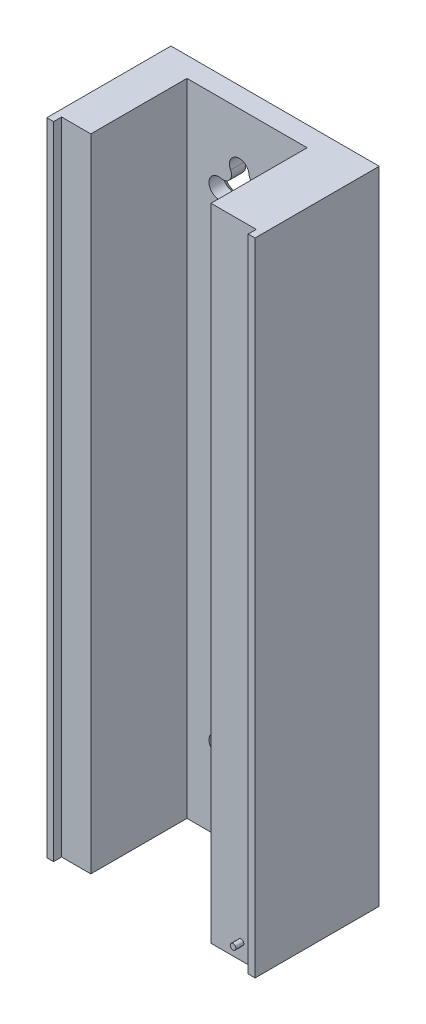
SolidWorks part; units mm, degrees
ref_plane "Top" through (0, 0, 0) normal (0, 0, 1) x (1, 0, 0)
ref_plane "Front" through (0, 0, 0) normal (0, 1, 0) x (1, 0, 0)
ref_plane "Right" through (0, 0, 0) normal (1, 0, 0) x (0, 0, -1)
sketch "Profile Sketch" plane through (0.0456, 0, -0.0242) normal (0, 1, 0) x (-1, 0, 0)
  line L0 (5.5456, -11.9758) -> (5.5456, 0.0242)
  line L1 (5.5456, 0.0242) -> (-0.1044, 0.0242)
  line L2 (-0.9544, 1.0242) -> (-0.9544, -14.4758)
  line L3 (-0.9544, -14.4758) -> (25.0456, -14.4758)
  line L4 (5.5456, -11.9758) -> (20.5456, -11.9758)
  line L5 (25.0456, -14.4758) -> (25.0456, 1.0242)
  line L6 (24.1956, 0.0242) -> (20.5456, 0.0242)
  line L7 (20.5456, 0.0242) -> (20.5456, -11.9758)
  line L8 (-0.1044, 0.0242) -> (-0.1044, 1.0242)
  line L9 (-0.9544, 1.0242) -> (-0.1044, 1.0242)
  line L10 (24.1956, 0.0242) -> (24.1956, 1.0242)
  line L11 (24.1956, 1.0242) -> (25.0456, 1.0242)
  line L12 (24.0456, 0.0242) -> (24.0456, 1.0242) construction
  dimension "Sprocket Height" = 1
  dimension "Tape Depth" = 12
  dimension "D8" = 0.15
  dimension "Reel Width" = 24
  dimension "D4" = 0.15
  dimension "Wall Thickness" = 1
  dimension "D1" = 14.5
  dimension "D2" = 5.5
  dimension "D3" = 3.5
extrude "Profile Extrude" add sketch "Profile Sketch" along normal blind 80
sketch "Sprocket Sketch" plane through (0, 0, 0) normal (0, 0, 1) x (1, 0, 0)
  line L0 (0.15, 80) -> (0.15, 0) construction
  circle A0 centre (-1.75, 2) radius 0.35
  dimension "D2" = 0.7
  dimension "D3" = 2
  dimension "D1" = 1.9
extrude "Sprocket Extrude" add sketch "Sprocket Sketch" along normal blind 1 contours A0
sketch "Magnet Hole Sketch" plane through (0, 0, -12) normal (0, 0, 1) x (1, 0, 0)
  line L0 (-13, 0) -> (-13, 10) construction
  line L1 (-20.5, 0) -> (-5.5, 0) construction
  line L2 (-13, 10) -> (-13, 13.5) construction
  line L3 (-13, 10) -> (-9.6713, 11.0816) construction
  circle A0 centre (-13, 10) radius 2.75 construction
  circle A1 centre (-13, 10) radius 4.75 construction
  arc A2 (-11.151, 12.9718) -> (-13, 13.5) centre (-11.9537, 13.6623) cw
  arc A3 (-11.151, 12.9718) -> (-9.6713, 11.0816) centre (-10.2234, 12.1737) cw
  circle A4 centre (-13, 10) radius 3.5 construction
  arc A5 (-9.6023, 9.1599) -> (-10.9428, 7.1684) centre (-10.0747, 8.031) cw
  arc A6 (-9.6023, 9.1599) -> (-9.6713, 11.0816) centre (-9.1936, 10.1366) cw
  arc A7 (-12.7491, 6.509) -> (-15.0572, 7.1684) centre (-13.9687, 6.6094) cw
  arc A8 (-12.7491, 6.509) -> (-10.9428, 7.1684) centre (-11.6938, 6.4222) cw
  arc A9 (-16.2426, 8.6826) -> (-16.3287, 11.0816) centre (-16.524, 9.8735) cw
  arc A10 (-16.2426, 8.6826) -> (-15.0572, 7.1684) centre (-15.9991, 7.6522) cw
  arc A11 (-15.2549, 12.6768) -> (-13, 13.5) centre (-14.2093, 13.3124) cw
  arc A12 (-15.2549, 12.6768) -> (-16.3287, 11.0816) centre (-16.1597, 12.1268) cw
  point P35 (-13, 10)
  dimension "D2" = 5.5
  dimension "D3" = 0.75
  dimension "D4" = 1.25
  dimension "D1" = 10
  dimension "D5" = 72
  dimension "D6" = 5
extrude "Magnet Cut" cut sketch "Magnet Hole Sketch" against normal through all
chamfer "Magnet Chamfer" distance 0.75 angle 45 10 edges at (-14.6289, 14.462, -14.5) (-15.2813, 11.5356, -14.5) (-12.2446, 12.6442, -14.5) (-17.7469, 9.8296, -14.5) (-9.2598, 12.928, -14.5) (-15.1654, 8.3048, -14.5) (-10.2518, 10.0986, -14.5) (-14.3049, 5.4327, -14.5) (-9.0595, 7.3477, -14.5) (-12.0569, 7.4168, -14.5)
ref_plane "Mid Plane" through (0, 40, 0) normal (0, -1, 0) x (-1, 0, 0)
mirror "Mirror2" about plane through (0, 40, 0) normal (0, -1, 0) of "Magnet Chamfer", "Magnet Cut"
equation "\"Tape Clearance\"= 0.15mm"
equation "\"D8@Profile Sketch\"=\"Tape Clearance\""
equation "\"D4@Profile Sketch\"=\"Tape Clearance\""
equation "\"D2@Sprocket Sketch\"=1.50mm - 2* \"Sprocket Clearance\""
equation "\"Sprocket Clearance\"= 0.4mm"
equation "\"D1@Sprocket Sketch\"=\"Tape Clearance\"+1.75"
